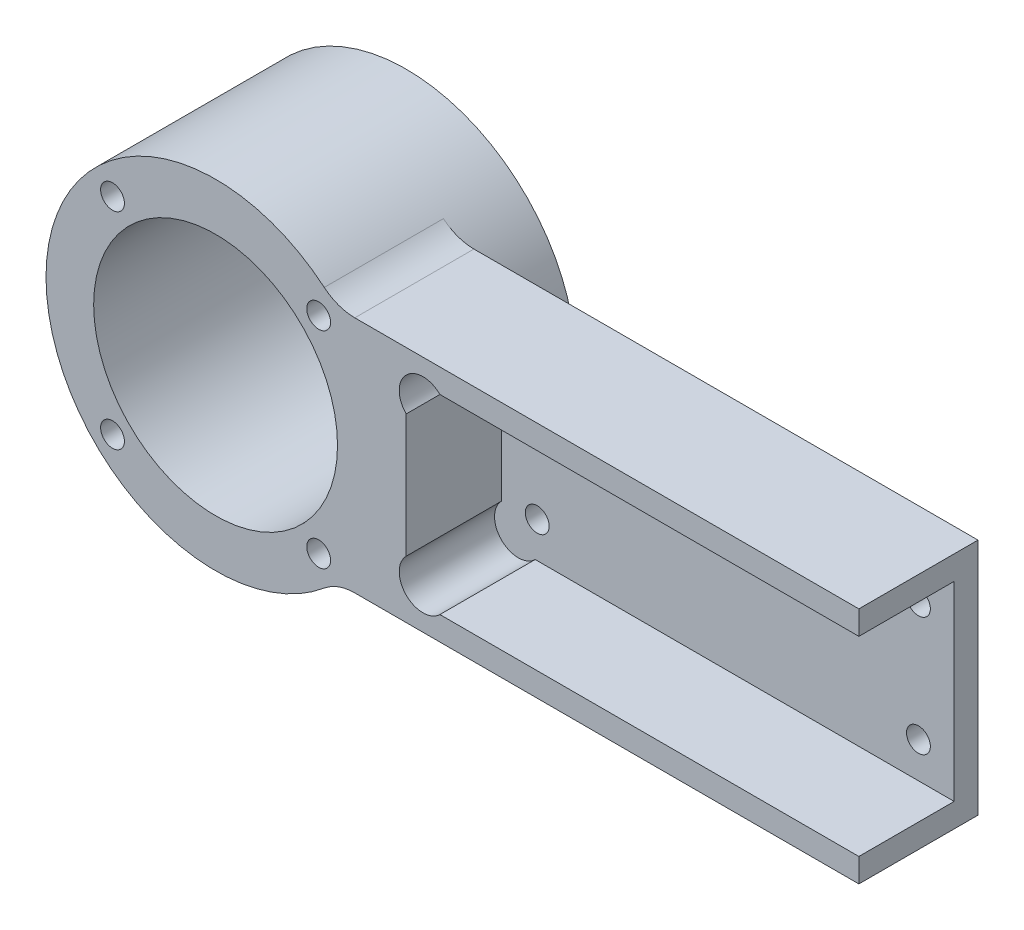
SolidWorks part; units mm, degrees
material "1060 Alloy"
ref_plane "Front Plane" through (0, 0, 0) normal (0, 0, 1) x (1, 0, 0)
ref_plane "Top Plane" through (0, 0, 0) normal (0, 1, 0) x (1, 0, 0)
ref_plane "Right Plane" through (0, 0, 0) normal (1, 0, 0) x (0, 0, -1)
sketch "Sketch1" plane through (0, 0, 0) normal (0, 0, 1) x (1, 0, 0)
  line L0 (32.1711, 31.75) -> (171.45, 31.75)
  line L1 (32.1711, -31.75) -> (171.45, -31.75)
  line L3 (171.45, 31.75) -> (171.45, 25.4)
  line L4 (171.45, -31.75) -> (171.45, -25.4)
  line L5 (171.45, 31.75) -> (171.45, -31.75) construction
  line L6 (171.45, 25.4) -> (50.8, 25.4)
  line L7 (50.8, 25.4) -> (50.8, -25.4)
  line L8 (50.8, -25.4) -> (171.45, -25.4)
  line L9 (171.45, 25.4) -> (171.45, -25.4)
  circle A0 centre (0, 0) radius 32.5
  arc A1 (32.1711, 31.75) -> (32.1711, -31.75) centre (0, 0) ccw
  point P3 (171.45, 0)
  dimension "D1" = 65
  dimension "D4" = 12.7
  dimension "D6" = 50.8
  dimension "D2" = 63.5
  dimension "D3" = 120.65
  dimension "D5" = 6.35
extrude "Boss-Extrude2" add sketch "Sketch1" along normal blind 6.35 contours L0 A1 L1 L4 L8 L7 L6 L3 A0 | L9 L6 L7 L8 region at (37.7479, 0, 0) region at (111.125, 0, 0)
extrude "Boss-Extrude3" add sketch "Sketch1<3>" along normal blind 25.4 from surface contours L0 A1 L1 L4 L8 L7 L6 L3 A0 region at (37.7479, 0, 0) starting at face at (82.4678, 0, 6.35)
sketch "Sketch1<3>" plane through (0, 0, 0) normal (0, 0, 1) x (1, 0, 0) same geometry as "Sketch1"
sketch "Sketch2" plane through (0, 0, 6.35) normal (0, 0, 1) x (1, 0, 0)
  line L0 (171.45, -25.4) -> (171.45, 25.4) construction
  line L1 (50.8, -25.4) -> (50.8, 25.4) construction
  line L2 (-27.4711, 27.4711) -> (0, 0) construction
  line L3 (0, 0) -> (-27.4711, -27.4711) construction
  line L4 (50.8, 25.4) -> (171.45, 25.4) construction
  line L5 (50.8, 25.4) -> (171.45, 25.4) construction
  line L6 (171.45, -25.4) -> (50.8, -25.4) construction
  line L7 (171.45, -25.4) -> (50.8, -25.4) construction
  line L8 (0, 0) -> (27.4711, 27.4711) construction
  line L11 (0, 0) -> (27.4711, -27.4711) construction
  line L13 (0, 0) -> (-32.5, 0) construction
  circle A0 centre (60.325, 15.875) radius 3.175
  circle A1 centre (161.925, 15.875) radius 3.175
  circle A2 centre (161.925, -15.875) radius 3.175
  circle A3 centre (60.325, -15.875) radius 3.175
  circle A4 centre (27.4711, 27.4711) radius 3.175
  circle A5 centre (27.4711, -27.4711) radius 3.175
  circle A6 centre (-27.4711, -27.4711) radius 3.175
  circle A7 centre (-27.4711, 27.4711) radius 3.175
  circle A8 centre (0, 0) radius 32.5 construction
  circle A15 centre (0, 0) radius 38.85 construction
  arc A16 (32.1711, 31.75) -> (32.1711, -31.75) centre (0, 0) ccw construction
  dimension "D1" = 6.35
  dimension "D2" = 6.35
  dimension "D4" = 9.525
  dimension "D5" = 9.525
  dimension "D6" = 9.525
  dimension "D3" = 9.525
  dimension "D7" = 9.525
  dimension "D8" = 9.525
  dimension "D11" = 45
  dimension "D12" = 45
extrude "Cut-Extrude1" cut sketch "Sketch2" against normal through all and the other way through all
sketch "Sketch3" plane through (0, 0, 31.75) normal (0, 0, 1) x (1, 0, 0)
  line L0 (50.8, 25.4) -> (59.7803, 16.4197) construction
  line L1 (50.8, 25.4) -> (171.45, 25.4) construction
  line L2 (50.8, 0) -> (32.5, 0) construction
  line L3 (50.8, -25.4) -> (50.8, 25.4) construction
  circle A0 centre (55.2901, 20.9099) radius 6.35
  circle A1 centre (0, 0) radius 32.5 construction
  circle A2 centre (55.2901, -20.9099) radius 6.35
  dimension "D1" = 12.7
  dimension "D2" = 45
extrude "Cut-Extrude2" cut sketch "Sketch3" against normal up to surface (25.4 mm away) up to face at (63.5, 15.875, 6.35)
sketch "Sketch4" plane through (0, 0, 0) normal (0, 0, -1) x (-1, 0, 0)
  line L0 (-31.75, 54.9926) -> (0, 0) construction
  line L1 (0, 0) -> (31.75, 54.9926) construction
  line L2 (-32.1711, -31.75) -> (-171.45, -31.75) construction
  line L3 (0, 0) -> (63.5, 0) construction
  line L4 (0, 0) -> (31.75, -54.9926) construction
  line L9 (-51.2937, 31.75) -> (-32.1711, 31.75)
  line L10 (-32.1711, 31.75) -> (-171.45, 31.75) construction
  line L11 (-32.1711, -31.75) -> (-51.2937, -31.75)
  line L12 (0, 0) -> (-63.5, 0) construction
  line L13 (0, 0) -> (-31.75, -54.9926) construction
  arc A1 (-40.8506, -48.6156) -> (-40.8506, 48.6156) centre (0, 0) ccw construction
  arc A2 (-20.7603, 56.6402) -> (-38.6717, 46.2991) centre (-31.75, 54.9926) ccw
  arc A8 (38.6717, 46.2991) -> (20.7603, 56.6402) centre (31.75, 54.9926) ccw
  arc A9 (59.432, -10.3411) -> (59.432, 10.3411) centre (63.5, 0) ccw
  arc A10 (20.7603, -56.6402) -> (38.6717, -46.2991) centre (31.75, -54.9926) ccw
  arc A11 (-38.6717, -46.2991) -> (-20.7603, -56.6402) centre (-31.75, -54.9926) ccw
  circle A13 centre (-31.75, 54.9926) radius 4.7625
  arc A14 (-38.6717, 46.2991) -> (-51.2937, 31.75) centre (0, 0) ccw
  circle A15 centre (31.75, 54.9926) radius 4.7625
  arc A16 (-32.1711, -31.75) -> (-32.1711, 31.75) centre (0, 0) ccw construction
  arc A17 (20.7603, 56.6402) -> (-20.7603, 56.6402) centre (0, 0) ccw
  circle A18 centre (63.5, 0) radius 4.7625
  circle A19 centre (31.75, -54.9926) radius 4.7625
  arc A20 (59.432, 10.3411) -> (38.6717, 46.2991) centre (0, 0) ccw
  arc A21 (38.6717, -46.2991) -> (59.432, -10.3411) centre (0, 0) ccw
  circle A22 centre (-31.75, -54.9926) radius 4.7625
  arc A23 (-20.7603, -56.6402) -> (20.7603, -56.6402) centre (0, 0) ccw
  arc A24 (-32.1711, -31.75) -> (-32.1711, 31.75) centre (0, 0) ccw
  arc A25 (-51.2937, -31.75) -> (-38.6717, -46.2991) centre (0, 0) ccw
  circle A26 centre (-63.5, 0) radius 4.7625
  point P48 (0, 0)
  dimension "D1" = 6.35
  dimension "D2" = 127
  dimension "D3" = 6
  dimension "D8" = 60.325
  dimension "D9" = 9.525
extrude "Boss-Extrude5" [suppressed] add sketch "Sketch4" against normal blind 6.35
fillet "Fillet1" radius 12.7 2 edges at (32.1711, -31.75, 15.875) (32.1711, 31.75, 15.875)
fillet "Fillet2" [suppressed] radius 12.7
sketch "Sketch5" plane through (0, 0, 0) normal (0, 0, -1) x (-1, 0, 0)
  arc A0 (-28.9644, -34.7002) -> (-28.9644, 34.7002) centre (0, 0) ccw construction
  arc A1 (-28.9644, -34.7002) -> (-28.9644, 34.7002) centre (0, 0) ccw
  circle A2 centre (-27.4711, -27.4711) radius 3.175 construction
  circle A3 centre (27.4711, -27.4711) radius 3.175 construction
  circle A4 centre (27.4711, 27.4711) radius 3.175 construction
  circle A5 centre (-27.4711, 27.4711) radius 3.175 construction
  circle A6 centre (0, 0) radius 32.5 construction
  circle A7 centre (-27.4711, -27.4711) radius 3.175
  circle A8 centre (27.4711, -27.4711) radius 3.175
  circle A9 centre (27.4711, 27.4711) radius 3.175
  circle A10 centre (-27.4711, 27.4711) radius 3.175
  circle A11 centre (0, 0) radius 32.5
  arc A12 (-28.9644, 34.7002) -> (-28.9644, -34.7002) centre (0, 0) ccw
  arc A13 (-28.9644, -34.7002) -> (-37.1027, -31.75) centre (-37.1027, -44.45) ccw construction
extrude "Boss-Extrude6" add sketch "Sketch5" along normal blind 19.05
sketch "Sketch6" plane through (0, 0, -19.05) normal (0, 0, -1) x (-1, 0, 0)
  circle A0 centre (0, 0) radius 32.5 construction
  circle A1 centre (0, 0) radius 32.5
  circle A2 centre (0, 0) radius 27.5
  dimension "D1" = 55
extrude "Boss-Extrude7" add sketch "Sketch6" against normal blind 2.54
sketch "Sketch7" plane through (0, 0, -19.05) normal (0, 0, -1) x (-1, 0, 0)
  circle A0 centre (0, 0) radius 67.6783
  dimension "D1" = 135.3566
